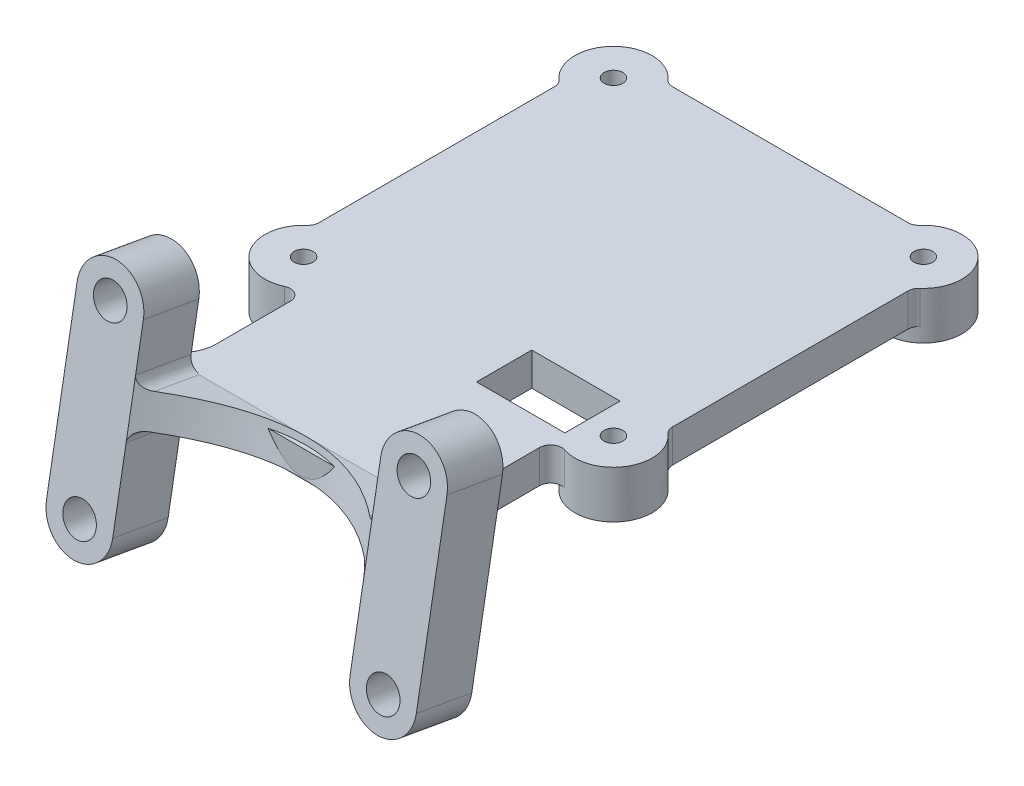
SolidWorks part; units mm, degrees
ref_plane "Front Plane" through (0, 0, 0) normal (0, 0, 1) x (1, 0, 0)
ref_plane "Top Plane" through (0, 0, 0) normal (0, 1, 0) x (1, 0, 0)
ref_plane "Right Plane" through (0, 0, 0) normal (1, 0, 0) x (0, 0, -1)
sketch "Sketch1" plane through (0, 0, 0) normal (0, 1, 0) x (1, 0, 0)
  line L0 (-16.0143, 16.0143) -> (-16.0143, 11.1488) construction
  line L1 (11.1488, 16.0143) -> (-11.1488, 16.0143)
  line L2 (16.0143, 11.1488) -> (16.0143, -11.1488)
  line L4 (-16.0143, 11.1488) -> (-16.0143, -11.1488)
  line L5 (16.0143, 16.0143) -> (-16.0143, -16.0143) construction
  line L6 (15.9857, -15.9857) -> (-16.0143, 16.0143) construction
  line L7 (-16.0143, 16.0143) -> (-11.1488, 16.0143) construction
  line L8 (16.0143, 16.0143) -> (16.0143, 11.0332) construction
  line L9 (16.0143, 16.0143) -> (11.1488, 16.0143) construction
  line L10 (15.9857, -15.9857) -> (11.6143, -15.9857) construction
  line L11 (15.9857, -15.9857) -> (16.0143, -11.1488) construction
  line L12 (-16.0143, -16.0143) -> (-16.0143, -11.1488) construction
  line L15 (11.6143, -11.0143) -> (3.6143, -11.0143)
  line L16 (11.6143, -11.0143) -> (11.6143, -15.9857)
  line L18 (3.6143, -11.0143) -> (3.6143, -16.0143)
  line L19 (11.6143, -11.0143) -> (3.6143, -16.0143) construction
  line L20 (11.6143, -15.9857) -> (3.6143, -11.0143) construction
  line L21 (11.6143, -15.9857) -> (11.6143, -16.0143)
  line L22 (-11.1488, -28.0143) -> (11.6143, -28.0143)
  line L23 (-11.1488, -28.0143) -> (-11.1488, -16.0143)
  line L24 (3.6143, -16.0143) -> (11.6143, -16.0143)
  line L25 (11.6143, -28.0143) -> (11.6143, -16.5629)
  line L26 (-11.1488, -28.0143) -> (11.6143, -16.0143) construction
  line L27 (-11.1488, -16.0143) -> (11.6143, -28.0143) construction
  circle A0 centre (14.0361, 14.0361) radius 0.85
  circle A1 centre (14.0361, -14.0361) radius 0.85
  circle A2 centre (-14.0361, -14.0361) radius 0.85
  circle A3 centre (-14.0361, 14.0361) radius 0.85
  arc A4 (-11.1488, 16.0143) -> (-16.0143, 11.1488) centre (-14.0361, 14.0361) ccw
  arc A5 (16.0143, 11.1488) -> (11.1488, 16.0143) centre (14.0361, 14.0361) ccw
  arc A6 (11.6143, -16.5629) -> (16.0143, -11.1488) centre (14.0361, -14.0361) ccw
  arc A7 (-16.0143, -11.1488) -> (-11.1488, -16.0143) centre (-14.0361, -14.0361) ccw
  point P0 (0, 0)
  point P3 (0.2328, -22.0143)
  point P8 (-13.435, -13.435)
  point P9 (13.435, 13.435)
  point P20 (7.6258, -13.5071)
  point P31 (0, 0)
  point P51 (0, 0)
  dimension "D3" = 1.7
  dimension "D5" = 3.5
  dimension "D7" = 12
  dimension "D1" = 32
  dimension "D4" = 39.7
  dimension "D8" = 12.4
  dimension "D9" = 8
  dimension "D10" = 5
  dimension "D2" = 45.2953
  dimension "D6" = 4
extrude "Boss-Extrude1" add sketch "Sketch1" along normal blind 2.9967
ref_plane "Plane1" through (0.2328, 0, 0) normal (1, 0, 0) x (0, 0, -1)
sketch "Sketch4" plane through (0, 0, 0) normal (0, -1, 0) x (1, 0, 0)
  line L3 (11.6143, 11.5092) -> (11.6143, 16.5629)
  circle A0 centre (-14.0361, -14.0361) radius 0.85 construction
  circle A1 centre (14.0361, -14.0361) radius 0.85 construction
  circle A2 centre (14.0361, 14.0361) radius 0.85 construction
  circle A3 centre (-14.0361, 14.0361) radius 0.85 construction
  circle A4 centre (-14.0361, -14.0361) radius 0.85
  circle A5 centre (14.0361, -14.0361) radius 0.85
  circle A6 centre (14.0361, 14.0361) radius 0.85
  circle A7 centre (-14.0361, 14.0361) radius 0.85
  circle A8 centre (-14.0361, 14.0361) radius 3.5
  arc A9 (11.6143, 11.5092) -> (11.6143, 16.5629) centre (14.0361, 14.0361) ccw
  circle A10 centre (14.0361, -14.0361) radius 3.5
  circle A11 centre (-14.0361, -14.0361) radius 3.5
extrude "Boss-Extrude3" add sketch "Sketch4" along normal blind 1.3
ref_plane "Plane3" through (0, 4.8811, 27.682) normal (0, 0.1736, 0.9848) x (1, 0, 0)
sketch "Sketch7" plane through (0, 4.8811, 27.682) normal (0, 0.1736, 0.9848) x (1, 0, 0)
  line L0 (0.2328, 0.7892) -> (0.2328, -10.5185) construction
  line L1 (0.2328, -4.8646) -> (-16.5172, -4.8646) construction
  line L2 (-10.5172, 3.1354) -> (-10.5172, -1.9135)
  line L3 (-16.5172, 3.1354) -> (-16.5172, -12.8646)
  line L4 (10.9828, 3.1354) -> (10.9828, -1.9135)
  line L5 (16.9828, 3.1354) -> (16.9828, -12.8646)
  line L6 (-11.1488, -4.8646) -> (11.6143, -4.8646) construction
  line L7 (-10.5172, -4.8646) -> (10.9828, -4.8646)
  line L8 (-10.5172, -1.9135) -> (10.9828, -1.9135)
  line L9 (10.9828, -4.8646) -> (10.9828, -12.8646)
  line L10 (-10.5172, -4.8646) -> (-10.5172, -12.8646)
  line L11 (-11.1488, -1.9135) -> (11.6143, -1.9135) construction
  line L12 (0.2328, -1.6482) -> (0.2328, 1.6482) construction
  circle A0 centre (-13.5172, 3.1354) radius 1.5
  arc A1 (-10.5172, 3.1354) -> (-16.5172, 3.1354) centre (-13.5172, 3.1354) ccw
  circle A2 centre (-13.5172, -12.8646) radius 1.5
  arc A3 (-10.5172, -12.8646) -> (-16.5172, -12.8646) centre (-13.5172, -12.8646) cw
  circle A4 centre (13.9828, -12.8646) radius 1.5
  arc A5 (10.9828, 3.1354) -> (16.9828, 3.1354) centre (13.9828, 3.1354) cw
  arc A6 (10.9828, -12.8646) -> (16.9828, -12.8646) centre (13.9828, -12.8646) ccw
  circle A7 centre (13.9828, 3.1354) radius 1.5
  point P10 (-16.5172, -4.8646)
  point P15 (-12.25, -4.8646)
  dimension "D1" = 3
  dimension "D2" = 1.5
  dimension "D3" = 27.5
  dimension "D4" = 16
extrude "Boss-Extrude5" add sketch "Sketch7" along normal blind 5 and the other way blind 0.1
sketch "Sketch9" plane through (0, -4.7907, 0.8447) normal (0, -0.9848, 0.1736) x (1, 0, 0)
  line L0 (-9.7672, 33.1091) -> (-9.7672, 28.1091) construction
  line L1 (-10.5172, 33.1091) -> (10.9828, 33.1091) construction
  line L2 (-9.7672, 28.1091) -> (10.2328, 28.1091) construction
  line L3 (0.2328, 28.1091) -> (0.2328, 33.1091) construction
  line L4 (10.2328, 33.1091) -> (10.2328, 28.1091) construction
  line L5 (-9.7672, 33.1091) -> (10.2328, 33.1091) construction
  line L6 (-10.5172, 33.1091) -> (10.9828, 33.1091)
  spline S0 degree 2 poles (-10.5172, 33.1091) (0.2328, 23.1091) (10.9828, 33.1091) knots 0 0 0 1 1 1
  dimension "D1" = 5
  dimension "D2" = 20
extrude "Cut-Extrude4" cut sketch "Sketch9" against normal through all both and the other way through all
sketch "Sketch11" plane through (0, 0, 28.0143) normal (0, 0, 1) x (1, 0, 0)
  line L4 (11.6143, 0) -> (11.6143, 2.4208)
  line L5 (11.6143, 2.4208) -> (-11.1488, 2.4208)
  line L6 (-11.1488, 2.4208) -> (-11.1488, 0)
  line L7 (-11.1488, 0) -> (11.6143, 0)
  line L8 (11.6143, 0) -> (11.6143, 2.4208)
  line L9 (11.6143, 2.4208) -> (-11.1488, 2.4208)
  line L10 (-11.1488, 2.4208) -> (-11.1488, 0)
  line L11 (-11.1488, 0) -> (11.6143, 0)
  dimension "D1" = 0
extrude "Boss-Extrude6" add sketch "Sketch11" along normal blind 0.5
fillet "Fillet3" radius 3 2 edges at (-11.1488, 1.4983, 28.177) (11.6143, 1.4983, 28.177)
fillet "Fillet4" radius 1 12 edges at (-16.0143, 1.4983, 11.1488) (-16.0143, 1.4983, -11.1488) (11.1488, 1.4983, -16.0143) (16.0143, 1.4983, -11.1488) (-11.1488, 1.4983, -16.0143) (16.0143, 1.4983, 11.1488) (11.6143, 1.4983, 16.5629) (-11.1488, 1.4983, 16.0143) (10.9828, 3.4308, 30.4763) (-10.5172, 3.4308, 30.4763) (10.9828, 0.5234, 30.9825) (-10.5172, 0.5234, 30.9825)
